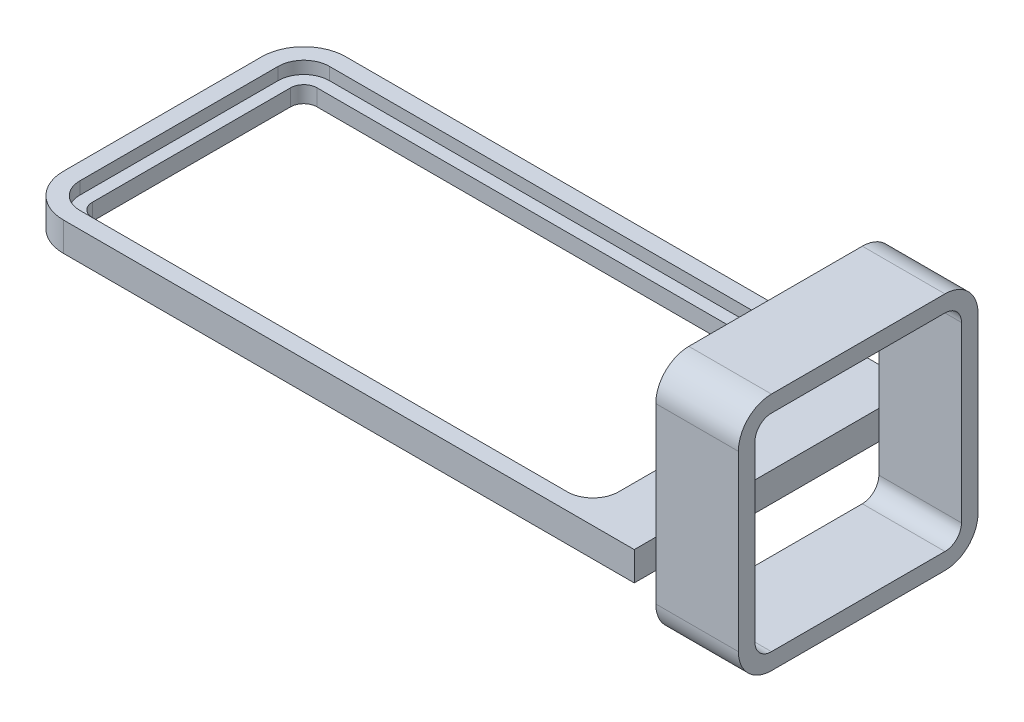
SolidWorks part; units mm, degrees
ref_plane "Front Plane" through (0, 0, 0) normal (0, 0, 1) x (1, 0, 0)
ref_plane "Top Plane" through (0, 0, 0) normal (0, 1, 0) x (1, 0, 0)
ref_plane "Right Plane" through (0, 0, 0) normal (1, 0, 0) x (0, 0, -1)
sketch "Sketch1" plane through (0, 0, 0) normal (0, 1, 0) x (1, 0, 0)
  line L0 (62, 0.1) -> (3, 0.1)
  line L1 (-0.1, -3) -> (-0.1, -27)
  line L2 (3, -30.1) -> (62, -30.1)
  line L3 (65.1, -27) -> (65.1, -3)
  line L4 (3, -30) -> (62, -30)
  line L5 (65, -27) -> (65, -3)
  line L6 (62, 0) -> (3, 0)
  line L7 (0, -3) -> (0, -27)
  line L8 (3, -30) -> (62, -30) construction
  line L9 (65, -27) -> (65, -3) construction
  line L10 (62, 0) -> (3, 0) construction
  line L11 (0, -3) -> (0, -27) construction
  arc A0 (3, 0.1) -> (-0.1, -3) centre (3, -3) ccw
  arc A1 (-0.1, -27) -> (3, -30.1) centre (3, -27) ccw
  arc A2 (62, -30.1) -> (65.1, -27) centre (62, -27) ccw
  arc A3 (65.1, -3) -> (62, 0.1) centre (62, -3) ccw
  arc A4 (62, -30) -> (65, -27) centre (62, -27) ccw
  arc A5 (65, -3) -> (62, 0) centre (62, -3) ccw
  arc A6 (3, 0) -> (0, -3) centre (3, -3) ccw
  arc A7 (0, -27) -> (3, -30) centre (3, -27) ccw
  arc A8 (62, -30) -> (65, -27) centre (62, -27) ccw construction
  arc A9 (65, -3) -> (62, 0) centre (62, -3) ccw construction
  arc A10 (3, 0) -> (0, -3) centre (3, -3) ccw construction
  arc A11 (0, -27) -> (3, -30) centre (3, -27) ccw construction
  dimension "D1" = 0
  dimension "D2" = 0.1
extrude "Extrude-Thin1" add sketch "Sketch1" along normal blind 1.5 and the other way blind 2 thin contours L1 A1 L2 A2 L3 A3 L0 A0 thin type one direction wall 2
ref_plane "Plane1" through (0, 1.5, 0) normal (0, 1, 0) x (1, 0, 0)
extrude "Extrude-Thin2" add sketch "Sketch1<3>" against normal up to surface (2 mm away) thin contours L0 A0 L1 A1 L2 A2 L3 A3 up to face at (32.5, -2, 15) wall 1.5
sketch "Sketch1<3>" plane through (0, 0, 0) normal (0, 1, 0) x (1, 0, 0) same geometry as "Sketch1"
sketch "Sketch2" plane through (0, 1.5, 0) normal (0, 1, 0) x (1, 0, 0)
  line L0 (67.1, -27) -> (67.1, -3) construction
  line L1 (67.1, -27) -> (67.1, -3)
  line L2 (62, 2.1) -> (72.1, 2.1)
  line L3 (72.1, 2.1) -> (72.1, -32.1)
  line L4 (72.1, -32.1) -> (62, -32.1)
  line L5 (62, 2.1) -> (3, 2.1) construction
  line L6 (3, -32.1) -> (62, -32.1) construction
  arc A0 (62, -32.1) -> (67.1, -27) centre (62, -27) ccw construction
  arc A1 (67.1, -3) -> (62, 2.1) centre (62, -3) ccw construction
  arc A2 (62, -32.1) -> (67.1, -27) centre (62, -27) ccw
  arc A3 (67.1, -3) -> (62, 2.1) centre (62, -3) ccw
  dimension "D1" = 5
extrude "Boss-Extrude2" add sketch "Sketch2" against normal up to surface (3.5 mm away) contours A3 L1 A2 L4 L3 L2 region at (69.377, 1.5, 15) up to face at (32.5, -2, 15)
ref_plane "Plane2" through (72.1, 0, 0) normal (1, 0, 0) x (0, 0, -1)
sketch "Sketch3" plane through (72.1, 0, 0) normal (1, 0, 0) x (0, 0, -1)
  line L0 (-15, 28.5588) -> (-15, -23.631) construction
  line L1 (-25.5, 19.5) -> (-4.5, 19.5)
  line L2 (-25.5, 17.5) -> (-4.5, 17.5)
  line L3 (-27.5, 15.5) -> (-27.5, -5.5)
  line L4 (-32.1, 1.5) -> (-32.1, -2)
  line L5 (-32.1, -2) -> (2.1, -2)
  line L6 (2.1, -2) -> (2.1, 1.5)
  line L7 (2.1, 1.5) -> (-32.1, 1.5)
  line L8 (-32.1, 1.5) -> (-32.1, -2) construction
  line L9 (-32.1, -2) -> (2.1, -2) construction
  line L10 (2.1, -2) -> (2.1, 1.5) construction
  line L11 (2.1, 1.5) -> (-32.1, 1.5) construction
  line L12 (-25.5, -7.5) -> (-4.5, -7.5)
  line L13 (-2.5, 15.5) -> (-2.5, -5.5)
  line L14 (-0.5, 15.5) -> (-0.5, -5.5)
  line L15 (-25.5, -9.5) -> (-4.5, -9.5)
  line L16 (-29.5, 15.5) -> (-29.5, -5.5)
  arc A0 (-27.5, -5.5) -> (-25.5, -7.5) centre (-25.5, -5.5) ccw
  arc A1 (-4.5, -7.5) -> (-2.5, -5.5) centre (-4.5, -5.5) ccw
  arc A2 (-2.5, 15.5) -> (-4.5, 17.5) centre (-4.5, 15.5) ccw
  arc A3 (-25.5, 17.5) -> (-27.5, 15.5) centre (-25.5, 15.5) ccw
  arc A4 (-0.5, 15.5) -> (-4.5, 19.5) centre (-4.5, 15.5) ccw
  arc A5 (-4.5, -9.5) -> (-0.5, -5.5) centre (-4.5, -5.5) ccw
  arc A6 (-29.5, -5.5) -> (-25.5, -9.5) centre (-25.5, -5.5) ccw
  arc A7 (-25.5, 19.5) -> (-29.5, 15.5) centre (-25.5, 15.5) ccw
  point P16 (-2.5, 17.5)
  point P19 (-27.5, 17.5)
  dimension "D4" = 2
  dimension "D2" = 25
  dimension "D3" = 16
  dimension "D1" = 0
  dimension "D5" = 2
extrude "Boss-Extrude3" add sketch "Sketch3" along normal blind 10 contours L1 A7 L16 A6 L15 A5 L14 A4 A3 L2 A2 L13 A1 L12 A0 L3 region at (72.1, 19.1587, 15) region at (72.1, -0.25, 28.5) region at (72.1, -0.25, 1.5) region at (72.1, -2.2995, 28.5)
